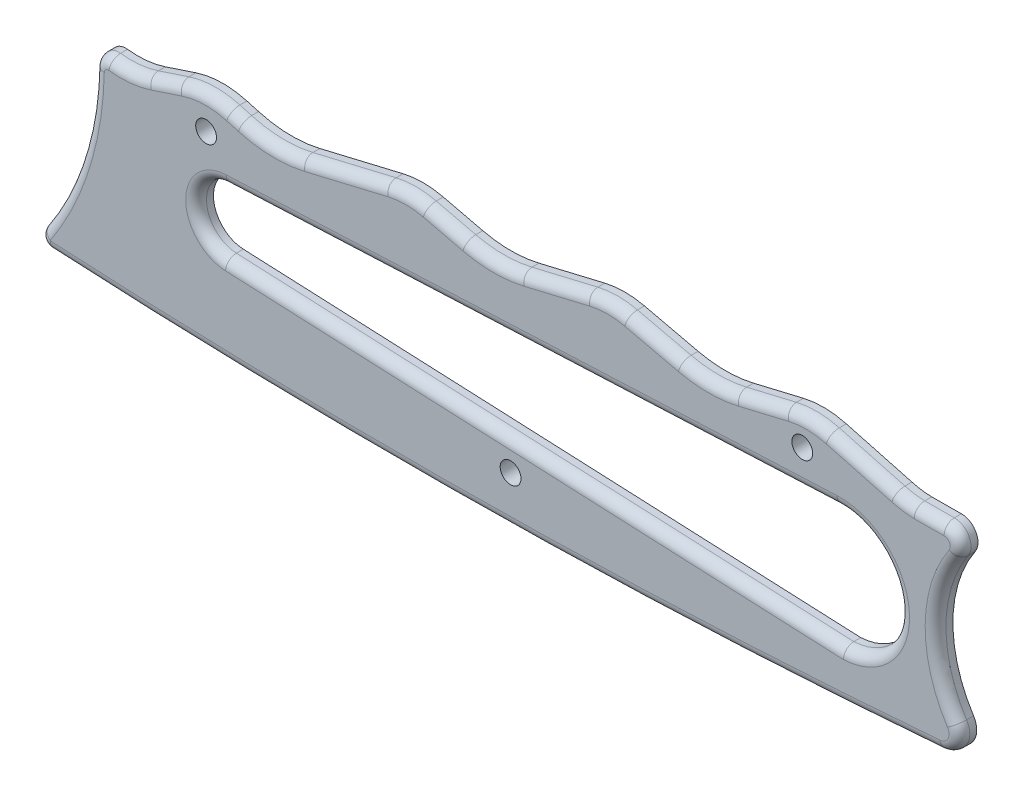
SolidWorks part; units mm, degrees
material "Natural Rubber"
ref_plane "Front Plane" through (0, 0, 0) normal (0, 0, 1) x (1, 0, 0)
ref_plane "Top Plane" through (0, 0, 0) normal (0, 1, 0) x (1, 0, 0)
ref_plane "Right Plane" through (0, 0, 0) normal (1, 0, 0) x (0, 0, -1)
sketch "Sketch1" plane through (0, 0, 0) normal (0, 0, 1) x (1, 0, 0)
  line L0 (30.3241, -1.771) -> (39.7808, -4.3058)
  line L1 (16.9637, -3.3738) -> (24.1557, -1.6676)
  line L2 (1.2316, -1.5966) -> (8.9649, -3.3927)
  line L3 (-13.9731, -3.8619) -> (-4.4818, -1.6101)
  line L4 (-27.7748, -2.4982) -> (-22.0697, -3.8578)
  line L5 (-45.5501, -5.3403) -> (-33.5581, -2.4952)
  line L6 (-56.0668, -4.6649) -> (-54.3765, -5.1455)
  line L7 (-67.8211, -6.2794) -> (-63.412, -4.8207)
  line L8 (42.6253, -4.7314) -> (46.906, -4.7047)
  line L9 (-56.5096, -14.3867) -> (31.5349, -10.3936)
  line L10 (32.4127, -27.4093) -> (-56.5781, -23.4189)
  arc A0 (24.1557, -1.6676) -> (30.3241, -1.771) centre (27.0368, -13.831) cw
  arc A1 (16.9637, -3.3738) -> (8.9649, -3.3927) centre (12.924, 13.6535) cw
  arc A2 (1.2316, -1.5966) -> (-4.4818, -1.6101) centre (-1.5963, -13.7725) ccw
  arc A3 (-22.0697, -3.8578) -> (-13.9731, -3.8619) centre (-18.0128, 13.1655) ccw
  arc A4 (-27.7748, -2.4982) -> (-33.5581, -2.4952) centre (-30.6726, -14.6576) ccw
  arc A5 (-54.3765, -5.1455) -> (-45.5501, -5.3403) centre (-49.5897, 11.6871) ccw
  arc A6 (-56.0668, -4.6649) -> (-63.412, -4.8207) centre (-59.4859, -16.6882) ccw
  arc A7 (-67.8211, -6.2794) -> (-73.2633, -6.8197) centre (-71.7472, 5.588) cw
  arc A8 (-75.6176, -8.8625) -> (-83.1472, -32.9028) centre (-120.6088, -7.9703) cw
  arc A9 (-83.1472, -32.9028) -> (-81.9522, -35.2884) centre (-81.8681, -33.7542) ccw
  arc A10 (-81.9522, -35.2884) -> (46.4603, -33.5026) centre (-30.7255, 898.9378) ccw
  arc A11 (48.6629, -29.0419) -> (48.8983, -8.4249) centre (64.4359, -18.9121) cw
  arc A12 (39.7808, -4.3058) -> (42.6253, -4.7314) centre (43.0405, 7.7617) ccw
  arc A13 (48.8983, -8.4249) -> (46.906, -4.7047) centre (46.9209, -7.0903) ccw
  arc A14 (46.4603, -33.5026) -> (48.6629, -29.0419) centre (46.2209, -30.6103) ccw
  arc A15 (-73.2633, -6.8197) -> (-75.6176, -8.8625) centre (-73.5181, -8.9042) ccw
  arc A16 (31.5349, -10.3936) -> (32.4127, -27.4093) centre (31.9209, -18.9042) cw
  arc A17 (-56.5781, -23.4189) -> (-56.5096, -14.3867) centre (-56.3681, -18.9042) cw
  circle A18 centre (26.4816, -5.3919) radius 1.5
  circle A19 centre (-59.446, -8.9183) radius 1.5
  circle A20 centre (-15.5623, -29.5695) radius 1.5
  point P53 (40.4402, -18.9042)
  point P54 (45.6902, -18.9121)
  point P55 (0, 0)
  point P56 (0, 0)
  dimension "D5" = 3
  dimension "D6" = 3
  dimension "D7" = 3
  dimension "D8" = 12.5
  dimension "D9" = 2.1
  dimension "D11" = 2.3856
  dimension "D12" = 12.5
  dimension "D13" = 2.9023
  dimension "D14" = 18.7457
  dimension "D2" = 86
  dimension "D3" = 48.5
  dimension "D4" = 48.5
  dimension "D10" = 4.2808
  dimension "D15" = 23.52
  dimension "D16" = 5.25
  dimension "D17" = 15
  dimension "D18" = 14.3
  dimension "D19" = 25.5
  dimension "D20" = 17.15
  dimension "D21" = 10
  dimension "D22" = 14.85
  dimension "D1" = 95.831
extrude "Boss-Extrude1" add sketch "Sketch1" along normal mid plane 2.5
fillet "Fillet1" radius 1.5 29 edges at (40.4289, -18.4652, 1.25) (-12.4874, -12.3901, 1.25) (-60.8876, -18.8699, 1.25) (41.1907, -4.6007, 1.25) (35.0524, -3.0384, 1.25) (27.2464, -1.3327, 1.25) (20.5597, -2.5207, 1.25) (12.9654, -3.8464, 1.25) (5.0983, -2.4947, 1.25) (-1.6259, -1.2726, 1.25) (-9.2275, -2.736, 1.25) (-18.0217, -4.3345, 1.25) (-24.9223, -3.178, 1.25) (-30.6663, -2.1576, 1.25) (-39.5541, -3.9178, 1.25) (-49.9758, -5.8087, 1.25) (-55.2217, -4.9052, 1.25) (-59.7511, -4.191, 1.25) (-65.6166, -5.5501, 1.25) (-70.5123, -6.8508, 1.25) (-74.8944, -7.3181, 1.25) (-77.6658, -21.4203, 1.25) (-83.2419, -34.4424, 1.25) (44.7657, -4.718, 1.25) (49.024, -5.964, 1.25) (45.6915, -18.6982, 1.25) (48.8232, -31.8952, 1.25) (-12.0827, -25.4141, 1.25) (-17.7153, -36.6014, 1.25)
